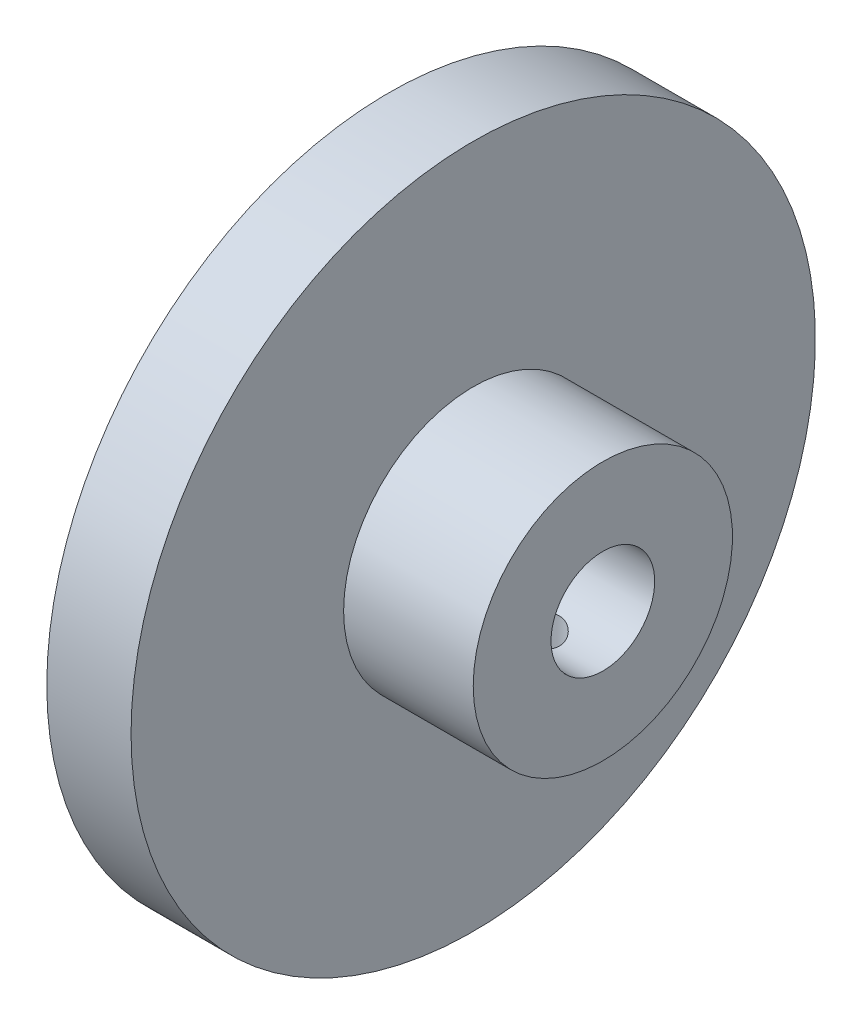
SolidWorks part; units mm, degrees
material "Brass"
ref_plane "Front Plane" through (0, 0, 0) normal (0, 0, 1) x (1, 0, 0)
ref_plane "Top Plane" through (0, 0, 0) normal (0, 1, 0) x (1, 0, 0)
ref_plane "Right Plane" through (0, 0, 0) normal (1, 0, 0) x (0, 0, -1)
sketch "Sketch1" plane through (0, 0, 0) normal (0, 1, 0) x (1, 0, 0)
  line L0 (-31.6089, 0) -> (66.0175, 0) construction
  line L3 (0, 4) -> (0, 26.4)
  line L4 (0, 26.4) -> (6.5, 26.4)
  line L5 (6.5, 26.4) -> (6.5, 10)
  line L6 (6.5, 10) -> (16.5, 10)
  line L7 (16.5, 10) -> (16.5, 4)
  line L8 (16.5, 4) -> (0, 4)
  dimension "D1" = 26.4
  dimension "D2" = 4
  dimension "D3" = 10
  dimension "D4" = 10
  dimension "D5" = 16.5
revolve "Revolve1" add sketch "Sketch1" angle 360 about L0
sketch "Sketch2" plane through (0, 0, 0) normal (0, 1, 0) x (1, 0, 0)
  line L0 (16.5, 10) -> (6.5, -10) construction
  line L1 (6.5, -10) -> (16.5, -10) construction
  line L2 (16.5, -10) -> (6.5, 10) construction
  line L3 (6.5, -26.4) -> (6.5, 26.4) construction
  line L4 (6.5, -10) -> (6.5, 10) construction
  line L5 (16.5, 10) -> (6.5, 10) construction
  circle A0 centre (11.5, 0) radius 1.65
  dimension "D1" = 3.3
extrude "Cut-Extrude1" cut sketch "Sketch2" against normal blind 10
